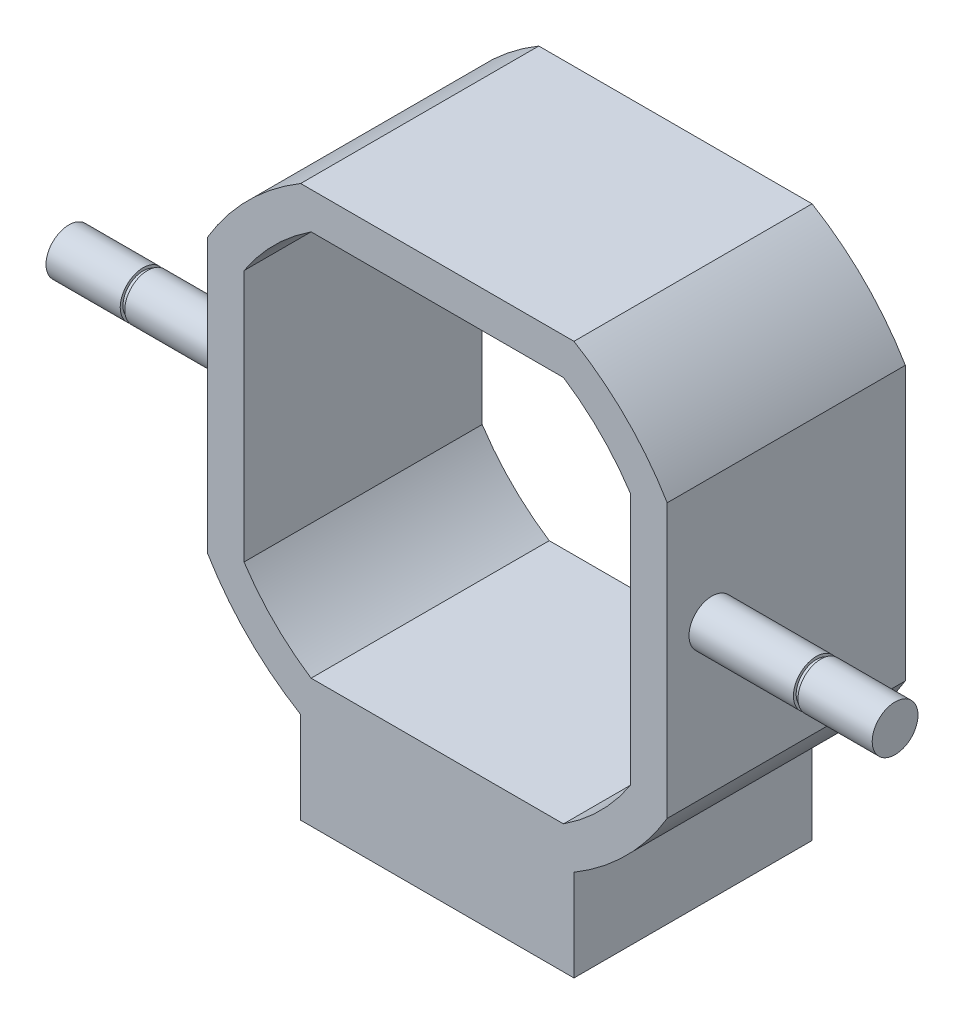
SolidWorks part; units mm, degrees
ref_plane "Płaszczyzna przednia" through (0, 0, 0) normal (0, 0, 1) x (1, 0, 0)
ref_plane "Płaszczyzna górna" through (0, 0, 0) normal (0, 1, 0) x (1, 0, 0)
ref_plane "Płaszczyzna prawa" through (0, 0, 0) normal (1, 0, 0) x (0, 0, -1)
sketch "Sketch1" plane through (0, 0, 0) normal (0, 0, 1) x (1, 0, 0)
  line L1 (-13.7779, 21.1) -> (13.7779, 21.1)
  line L2 (-21.1, 13.7779) -> (-21.1, -13.7779)
  line L3 (-13.7779, -21.1) -> (13.7779, -21.1)
  line L4 (21.1, 13.7779) -> (21.1, -13.7779)
  line L5 (-17.8191, 17.8191) -> (17.8191, -17.8191) construction
  line L6 (-17.8191, -17.8191) -> (17.8191, 17.8191) construction
  arc A0 (-13.7779, 21.1) -> (-21.1, 13.7779) centre (0, 0) ccw
  arc A1 (21.1, 13.7779) -> (13.7779, 21.1) centre (0, 0) ccw
  arc A2 (13.7779, -21.1) -> (21.1, -13.7779) centre (0, 0) ccw
  arc A3 (-21.1, -13.7779) -> (-13.7779, -21.1) centre (0, 0) ccw
  point P0 (0, 0)
  dimension "D3" = 50.4
  dimension "D1" = 27.5558
  dimension "D2" = 27.5558
  dimension "D4" = 27.5558
  dimension "D5" = 27.5558
extrude "Extrude-Thin1" add sketch "Sketch1" along normal blind 26 thin thin type one direction wall 4
sketch "Sketch2" plane through (-25.1, 0, 0) normal (-1, 0, 0) x (0, 0, 1)
  line L0 (26, 14.9208) -> (26, -14.9208) construction
  line L1 (26, -21.1) -> (0, -21.1) construction
  line L2 (26, -21.1) -> (0, -21.1)
  circle A0 centre (21.12, 1.16) radius 2.5
  dimension "D1" = 5
  dimension "D2" = 4.88
  dimension "D3" = 22.26
extrude "Boss-Extrude1" add sketch "Sketch2" along normal blind 20 separate body contours A0 region at (-25.1, 1.16, 21.12)
extrude "Boss-Extrude2" add sketch "Sketch2<3>" against normal blind 20 from surface contours A0 region at (-25.1, 1.16, 21.12) starting at face at (25.1, 0, 13)
sketch "Sketch2<3>" plane through (-25.1, 0, 0) normal (-1, 0, 0) x (0, 0, 1) same geometry as "Sketch2"
sketch "Sketch3" plane through (0, -25.1, 0) normal (0, -1, 0) x (1, 0, 0)
  line L0 (14.9208, 26) -> (14.9208, 0) construction
  line L1 (-14.9208, 0) -> (14.9208, 0) construction
  line L2 (-14.9208, 26) -> (-14.9208, 0) construction
  line L3 (-14.9208, 26) -> (14.9208, 26) construction
  line L4 (14.9208, 26) -> (14.9208, 0)
  line L5 (-14.9208, 0) -> (14.9208, 0)
  line L6 (-14.9208, 26) -> (-14.9208, 0)
  line L7 (-14.9208, 26) -> (14.9208, 26)
extrude "Boss-Extrude3" add sketch "Sketch3" along normal blind 10
sketch "Szkic1" plane through (45.1, 0, 0) normal (1, 0, 0) x (0, 0, -1)
  circle A0 centre (-21.12, 1.16) radius 2.5
  circle A1 centre (-21.12, 1.16) radius 2.2
  dimension "D1" = 4.4
  dimension "D2" = 5
extrude "Wytnij-wyciągnięcie1" cut sketch "Szkic1" along normal blind 0.5 from offset 8.6 offset against normal yes
sketch "Szkic2" plane through (-45.1, 0, 0) normal (-1, 0, 0) x (0, 0, 1)
  circle A0 centre (21.12, 1.16) radius 2.5
  circle A1 centre (21.12, 1.16) radius 2.2
  dimension "D1" = 4.4
  dimension "D2" = 5
extrude "Wytnij-wyciągnięcie2" cut sketch "Szkic2" along normal blind 0.5 from offset 8.6 offset against normal yes
